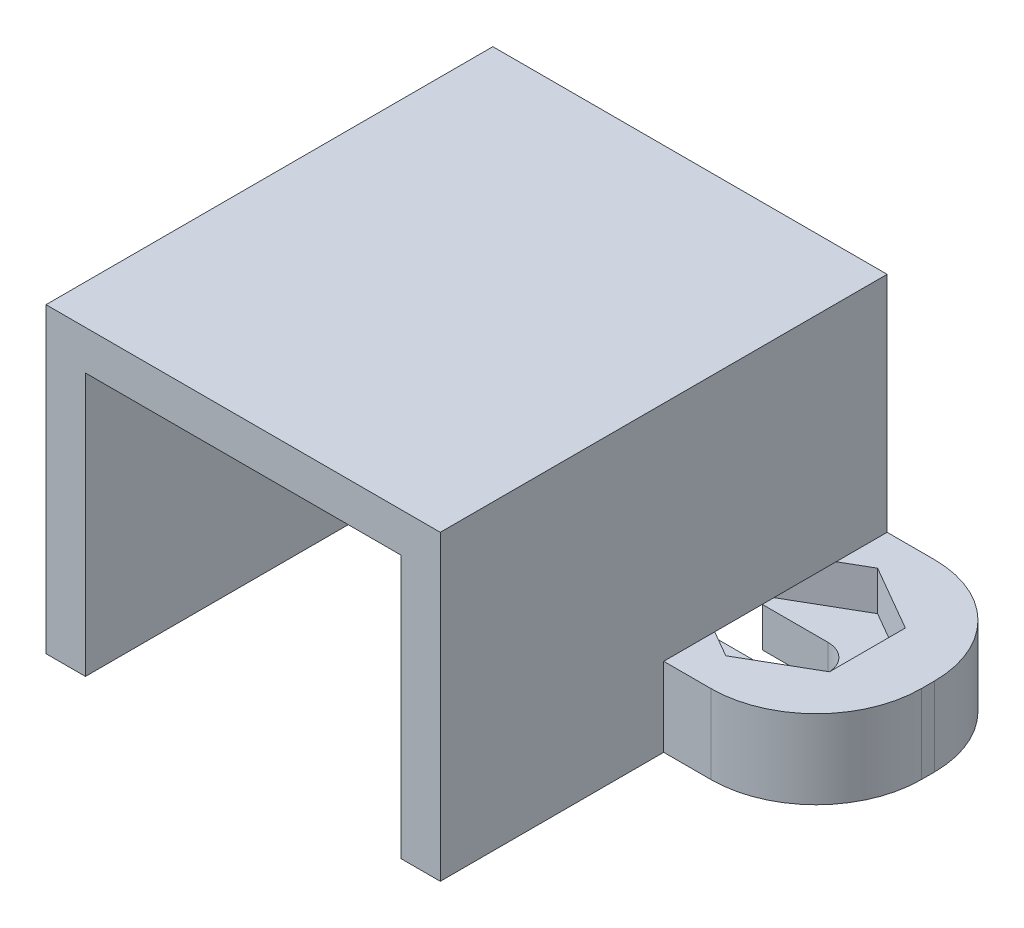
SolidWorks part; units mm, degrees
ref_plane "Front Plane" through (0, 0, 0) normal (0, 0, 1) x (1, 0, 0)
ref_plane "Top Plane" through (0, 0, 0) normal (0, 1, 0) x (1, 0, 0)
ref_plane "Right Plane" through (0, 0, 0) normal (1, 0, 0) x (0, 0, -1)
sketch "Sketch1" plane through (0, 0, 0) normal (0, 0, 1) x (1, 0, 0)
  line L0 (0, 0) -> (1.5, 0)
  line L1 (1.5, 0) -> (1.5, 10)
  line L2 (0, 0) -> (0, 10)
  line L3 (0, 10) -> (0, 11.5)
  line L4 (0, 11.5) -> (15, 11.5)
  line L5 (15, 11.5) -> (15, 0)
  line L6 (15, 0) -> (13.5, 0)
  line L7 (13.5, 0) -> (13.5, 10)
  line L8 (13.5, 10) -> (1.5, 10)
extrude "Boss-Extrude1" add sketch "Sketch1" along normal blind 17
sketch "Sketch10" plane through (0, 10, 0) normal (0, -1, 0) x (1, 0, 0)
  line L0 (13.5, 17) -> (13.5, 16) construction
  line L2 (13.5, 17) -> (13.5, 0) construction
  line L3 (13.5, 16) -> (13.5, 12) construction
  line L4 (13.5, 12) -> (13.5, 11) construction
  line L5 (13.5, 11) -> (13.5, 9) construction
  line L6 (13.5, 9) -> (13.5, 8) construction
  line L8 (13.5, 16) -> (10.5, 16)
  line L9 (13.5, 16) -> (13.5, 12)
  line L10 (13.5, 12) -> (10.5, 12)
  line L11 (10.5, 16) -> (10.5, 12)
  line L12 (13.5, 11) -> (10.5, 11)
  line L13 (13.5, 11) -> (13.5, 9)
  line L14 (13.5, 9) -> (10.5, 9)
  line L15 (10.5, 11) -> (10.5, 9)
extrude "Boss-Extrude8" add sketch "Sketch10" along normal blind 0.4
sketch "Sketch11" plane through (13.5, 0, 0) normal (-1, 0, 0) x (0, 0, 1)
  line L0 (11, 9.6) -> (9, 9.6) construction
  line L1 (9, 9.6) -> (11, 9.6)
  line L2 (9, 9.6) -> (9, 7.5)
  line L3 (9, 7.5) -> (11, 7.5)
  line L4 (11, 9.6) -> (11, 7.5)
  line L5 (9, 9.6) -> (9, 10) construction
  line L6 (12, 9.6) -> (16, 9.6) construction
  line L7 (12, 9.6) -> (16, 9.6)
  line L8 (12, 9.6) -> (12, 7.5)
  line L9 (12, 7.5) -> (16, 7.5)
  line L10 (16, 9.6) -> (16, 7.5)
  line L11 (16, 9.6) -> (12, 9.6) construction
extrude "Boss-Extrude9" add sketch "Sketch11" along normal blind 0.4
fillet "Fillet5" radius 0.4 2 edges at (13.1, 9.6, 14) (13.1, 9.6, 10)
sketch "Sketch12" plane through (0, 0, 0) normal (0, -1, 0) x (1, 0, 0)
  line L2 (15, 8) -> (0, 8)
  line L3 (15, 17) -> (15, 0) construction
  line L4 (0, 17) -> (0, 0) construction
split "Split2" trim tools "Sketch12" bodies to split 115 resulting bodies 116 117
fillet "Fillet6" radius 1.5 2 edges at (1.5, 10, 4) (13.5, 10, 4)
combine bodies "Combine2" operation type add bodies to combine 116 117
sketch "Sketch13" plane through (0, 0, 0) normal (0, -1, 0) x (1, 0, 0)
  line L0 (7.5, 0) -> (7.5, 1.8013) construction
  line L1 (0, 0) -> (-5.8, 0)
  line L2 (0, 0) -> (0, 8.5)
  line L3 (0, 8.5) -> (-5.8, 8.5)
  line L4 (-5.8, 0) -> (-5.8, 8.5)
  line L5 (3, 0) -> (12, 0) construction
  line L6 (20.8, 0) -> (20.8, 8.5)
  line L7 (15, 8.5) -> (20.8, 8.5)
  line L8 (15, 0) -> (15, 8.5)
  line L9 (15, 0) -> (20.8, 0)
extrude "Boss-Extrude10" add sketch "Sketch13" against normal blind 3
fillet "Fillet7" radius 4 4 edges at (20.8, 1.5, 8.5) (20.8, 1.5, 0) (-5.8, 1.5, 0) (-5.8, 1.5, 8.5)
sketch "Sketch15" plane through (0, 0, 0) normal (-1, 0, 0) x (0, 0, 1)
  line L0 (0, 3) -> (17, 3)
  line L1 (17, 11.5) -> (17, 0) construction
split "Split3" trim tools "Sketch15" bodies to split 120 resulting bodies 121 122 123
sketch "Sketch16" plane through (0, 3, 0) normal (0, 1, 0) x (1, 0, 0)
  line L0 (1.5, -4.25) -> (-1, -4.25) construction
  line L1 (1.5, 0) -> (1.5, -17) construction
  line L2 (13.5, 0) -> (1.5, 0) construction
  line L3 (-1, -7.1368) -> (1.5, -5.6934)
  line L4 (1.5, -5.6934) -> (1.5, -2.8066)
  line L5 (1.5, -2.8066) -> (-1, -1.3632)
  line L6 (-1, -1.3632) -> (-3.5, -2.8066)
  line L7 (-3.5, -2.8066) -> (-3.5, -5.6934)
  line L8 (-3.5, -5.6934) -> (-1, -7.1368)
  line L9 (7.5, 0) -> (7.5, -2.8066) construction
  line L14 (13.5, -4.25) -> (16, -4.25) construction
  line L15 (16, -1.3632) -> (13.5, -2.8066)
  line L16 (13.5, -5.6934) -> (16, -7.1368)
  line L17 (16, -7.1368) -> (18.5, -5.6934)
  line L18 (18.5, -2.8066) -> (16, -1.3632)
  line L20 (18.5, -2.8066) -> (18.5, -5.6934)
  line L23 (13.5, -5.6934) -> (13.5, -2.8066)
  circle A0 centre (-1, -4.25) radius 2.5 construction
  circle A1 centre (16, -4.25) radius 2.5 construction
extrude "Cut-Extrude1" cut sketch "Sketch16" against normal blind 1.5
sketch "Sketch17" plane through (0, 1.5, 0) normal (0, 1, 0) x (1, 0, 0)
  line L0 (-1, -1.3632) -> (-1, -7.1368) construction
  line L3 (7.5, 0) -> (7.5, -1.3632) construction
  line L4 (15, 0) -> (0, 0) construction
  line L5 (16, -1.3632) -> (16, -7.1368) construction
  line L6 (16, -5.25) -> (13.5, -5.25)
  line L7 (13.5, -8) -> (13.5, 0) construction
  line L8 (16, -3.25) -> (13.5, -3.25)
  line L9 (13.5, -3.25) -> (13.5, -5.25)
  line L10 (1.5, -3.25) -> (1.5, -5.25)
  line L11 (-1, -3.25) -> (1.5, -3.25)
  line L12 (-1, -5.25) -> (1.5, -5.25)
  arc A0 (-1, -3.25) -> (-1, -5.25) centre (-1, -4.25) ccw
  arc A1 (16, -3.25) -> (16, -5.25) centre (16, -4.25) cw
extrude "Cut-Extrude2" cut sketch "Sketch17" against normal through all
combine bodies "Combine3" operation type add bodies to combine 123 128 127
